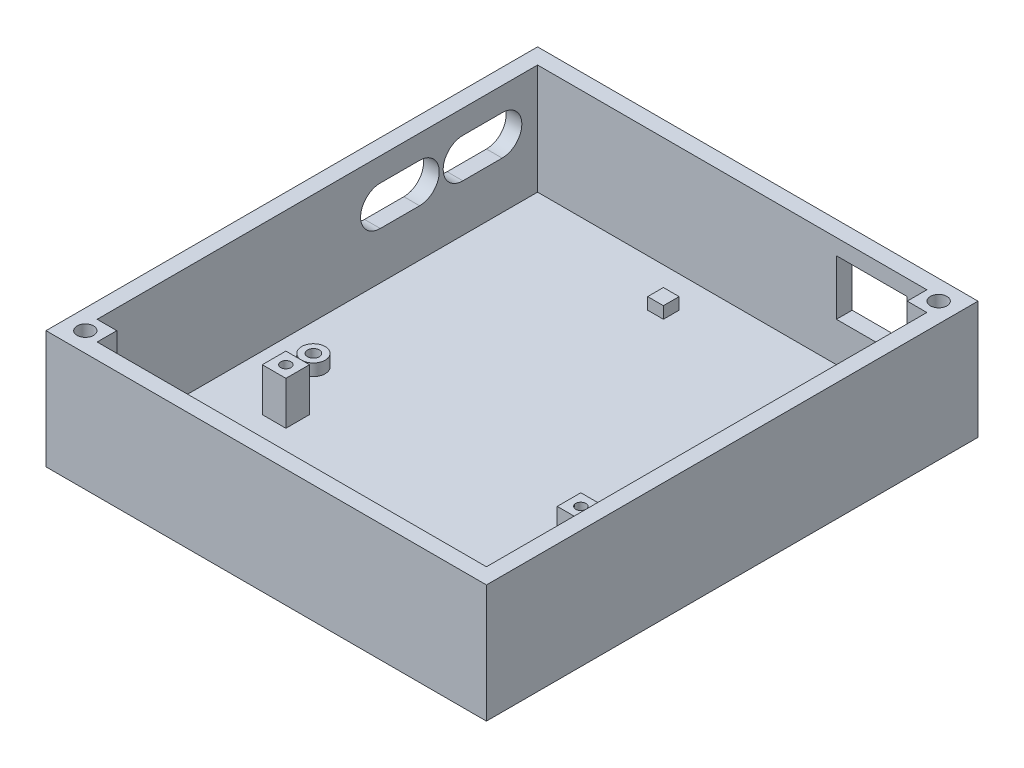
SolidWorks part; units mm, degrees
ref_plane "Front Plane" through (0, 0, 0) normal (0, 0, 1) x (1, 0, 0)
ref_plane "Top Plane" through (0, 0, 0) normal (0, 1, 0) x (1, 0, 0)
ref_plane "Right Plane" through (0, 0, 0) normal (1, 0, 0) x (0, 0, -1)
sketch "Sketch1" plane through (0, 0, 0) normal (0, 1, 0) x (1, 0, 0)
  line L1 (-56, -62.5) -> (56, -62.5)
  line L2 (-56, -62.5) -> (-56, 62.5)
  line L3 (-56, 62.5) -> (56, 62.5)
  line L4 (56, -62.5) -> (56, 62.5)
  line L5 (-56, -62.5) -> (56, 62.5) construction
  line L6 (-56, 62.5) -> (56, -62.5) construction
  point P0 (0, 0)
  dimension "D1" = 112
  dimension "D2" = 125
extrude "Boss-Extrude1" add sketch "Sketch1" along normal blind 2
sketch "Sketch2" plane through (0, 2, 0) normal (0, 1, 0) x (1, 0, 0)
  line L0 (-56, -62.5) -> (56, -62.5) construction
  line L1 (-12, 50.5) -> (-8, 50.5) construction
  line L2 (-12, 50.5) -> (-12, 46.5) construction
  line L3 (-12, 46.5) -> (-8, 46.5) construction
  line L4 (52, 53.5) -> (47, 53.5)
  line L5 (-8, 50.5) -> (-8, 46.5) construction
  line L6 (-56, 62.5) -> (-56, -62.5) construction
  line L7 (47, 53.5) -> (47, 58.5)
  line L8 (52, -58.5) -> (52, 58.5)
  line L9 (52, 58.5) -> (-52, 58.5)
  line L10 (-52, 58.5) -> (-52, -58.5)
  line L11 (-52, -58.5) -> (52, -58.5)
  line L12 (52, -58.5) -> (52, 53.5)
  line L13 (47, 58.5) -> (-52, 58.5)
  line L14 (-52, 58.5) -> (-52, -53.5)
  line L15 (-47, -58.5) -> (52, -58.5)
  line L16 (56, 62.5) -> (-56, 62.5) construction
  line L29 (-47, -58.5) -> (-47, -53.5)
  line L30 (-47, -53.5) -> (-52, -53.5)
  line L31 (56, -62.5) -> (56, 62.5) construction
  circle A0 centre (-42, -8.5) radius 1.5 construction
  circle A1 centre (38, -8.5) radius 1.5 construction
  circle A2 centre (-51, -57.5) radius 2.1
  circle A3 centre (51, 57.5) radius 2.1
  point P8 (0, 0)
  point P16 (54.7195, 58.7926)
  point P21 (-54.2044, -58.5)
  line M12 (56, -62.5) -> (56, 62.5)
  line M13 (56, 62.5) -> (-56, 62.5)
  line M14 (-56, 62.5) -> (-56, -62.5)
  line M15 (-56, -62.5) -> (56, -62.5)
  dimension "D1" = 3
  dimension "D13" = 4.2
  dimension "D15" = 4.2
  dimension "D18" = 5
  dimension "D2" = 80
  dimension "D3" = 5
  dimension "D5" = 8
  dimension "D6" = 62
  dimension "D7" = 5
  dimension "D8" = 14
  dimension "D9" = 4
  dimension "D10" = 4
  dimension "D11" = 40
  dimension "D12" = 5
  dimension "D14" = 5
  dimension "D16" = 5
  dimension "D17" = 5
  dimension "D4" = 4
extrude "Boss-Extrude2" add sketch "Sketch2" along normal blind 10 contours A0 | A1 | A3 A2 L29 L30 L14 L13 L7 L4 L12 L15 M15 M12 M13 M14 region at (48.9478, 2, -55.4478) region at (-48.9478, 2, 55.4478) region at (0, 2, 60.8216)
sketch "Sketch3" plane through (0, 2, 0) normal (0, 1, 0) x (1, 0, 0)
  line L0 (-32, -50.5) -> (-32, -25.5) construction
  line L1 (-35, -53.5) -> (40, -53.5) construction
  line L2 (-35, -53.5) -> (-35, -22.5) construction
  line L3 (-35, -22.5) -> (40, -22.5) construction
  line L4 (40, -53.5) -> (40, -22.5) construction
  line L5 (-32, -25.5) -> (37, -25.5) construction
  line L6 (37, -50.5) -> (37, -25.5) construction
  line L7 (-32, -50.5) -> (37, -50.5) construction
  line L8 (-38, -19.5) -> (43, -19.5)
  line L9 (43, -56.5) -> (43, -19.5)
  line L10 (-38, -56.5) -> (43, -56.5)
  line L11 (-38, -56.5) -> (-38, -19.5)
  line L12 (-47, -58.5) -> (52, -58.5) construction
  line L13 (-47, -58.5) -> (52, -58.5) construction
  line L14 (-32, -25.5) -> (-38, -25.5)
  line L15 (-32, -50.5) -> (-38, -50.5)
  line L16 (37, -25.5) -> (43, -25.5)
  line L17 (37, -50.5) -> (43, -50.5)
  line L18 (37, -25.5) -> (37, -19.5)
  line L19 (37, -50.5) -> (37, -56.5)
  line L20 (-32, -50.5) -> (-32, -56.5)
  line L21 (-32, -19.5) -> (-32, -25.5)
  circle A0 centre (-35, -22.5) radius 1.3
  circle A1 centre (40, -22.5) radius 1.3
  circle A2 centre (40, -53.5) radius 1.3
  circle A3 centre (-35, -53.5) radius 1.3
  point P17 (2.5, -22.5)
  point P19 (2.5, -58.5)
  dimension "D3" = 2.6
  dimension "D4" = 75
  dimension "D5" = 31
  dimension "D6" = 5
  dimension "D1" = 3
  dimension "D2" = 3
extrude "Boss-Extrude3" add sketch "Sketch3" along normal blind 11 contours L20 L15 L11 L10 A3 | L21 L8 L11 L14 A0 | L18 L16 L9 L8 A1 | L17 L19 L10 L9 A2 region at (-35, 2, 19.5849) region at (40, 2, 19.5849) region at (-35, 2, 50.5849) region at (42.9151, 2, 53.5)
sketch "Sketch5" plane through (0, 2, 0) normal (0, 1, 0) x (1, 0, 0)
  line L0 (-8, 50.5) -> (-8, 46.5) construction
  line L1 (-12, 50.5) -> (-8, 50.5) construction
  line L2 (-12, 50.5) -> (-12, 46.5) construction
  line L3 (-12, 46.5) -> (-8, 46.5) construction
  line L4 (-8, 50.5) -> (-8, 46.5)
  line L5 (-12, 50.5) -> (-8, 50.5)
  line L6 (-12, 50.5) -> (-12, 46.5)
  line L7 (-12, 46.5) -> (-8, 46.5)
  circle A0 centre (-42, -8.5) radius 3
  circle A1 centre (38, -8.5) radius 3
  circle A2 centre (38, -8.5) radius 1.5 construction
  circle A3 centre (38, -8.5) radius 1.5
  circle A4 centre (-42, -8.5) radius 1.5 construction
  circle A5 centre (-42, -8.5) radius 1.5
  dimension "D1" = 6
extrude "Boss-Extrude4" add sketch "Sketch5" along normal blind 3
sketch "Sketch6" plane through (0, 13, 0) normal (0, 1, 0) x (1, 0, 0)
  line L4 (-32, -56.5) -> (-32, -50.5)
  line L5 (-32, -50.5) -> (-38, -50.5)
  line L6 (-38, -50.5) -> (-38, -56.5)
  line L7 (-38, -56.5) -> (-32, -56.5)
  line L8 (-32, -56.5) -> (-32, -50.5)
  line L9 (-32, -50.5) -> (-38, -50.5)
  line L10 (-38, -50.5) -> (-38, -56.5)
  line L11 (-38, -56.5) -> (-32, -56.5)
  line L12 (37, -19.5) -> (37, -25.5)
  line L13 (37, -25.5) -> (43, -25.5)
  line L14 (43, -25.5) -> (43, -19.5)
  line L15 (43, -19.5) -> (37, -19.5)
  line L16 (37, -19.5) -> (37, -25.5)
  line L17 (37, -25.5) -> (43, -25.5)
  line L18 (43, -25.5) -> (43, -19.5)
  line L19 (43, -19.5) -> (37, -19.5)
  line L20 (43, -50.5) -> (37, -50.5)
  line L21 (37, -50.5) -> (37, -56.5)
  line L22 (37, -56.5) -> (43, -56.5)
  line L23 (43, -56.5) -> (43, -50.5)
  line L24 (43, -50.5) -> (37, -50.5)
  line L25 (37, -50.5) -> (37, -56.5)
  line L26 (37, -56.5) -> (43, -56.5)
  line L27 (43, -56.5) -> (43, -50.5)
  circle A0 centre (40, -53.5) radius 1.3 construction
  circle A1 centre (40, -22.5) radius 1.3
  circle A2 centre (40, -22.5) radius 1.3
  circle A3 centre (-35, -53.5) radius 1.3 construction
  circle A4 centre (40, -53.5) radius 1.3
  circle A5 centre (-35, -53.5) radius 1.3
  dimension "D1" = 0
  dimension "D2" = 0
  dimension "D3" = 0
  dimension "D4" = 0
extrude "Boss-Extrude5" add sketch "Sketch6" along normal blind 6.3
sketch "Sketch7" plane through (0, 12, 0) normal (0, 1, 0) x (1, 0, 0)
  line L4 (-56, -62.5) -> (56, -62.5)
  line L5 (56, -62.5) -> (56, 62.5)
  line L6 (56, 62.5) -> (-56, 62.5)
  line L7 (-56, 62.5) -> (-56, -62.5)
  line L8 (-56, -62.5) -> (56, -62.5)
  line L9 (56, -62.5) -> (56, 62.5)
  line L10 (56, 62.5) -> (-56, 62.5)
  line L11 (-56, 62.5) -> (-56, -62.5)
  circle M5 centre (51, 57.5) radius 2.1
  line M6 (47, 53.5) -> (52, 53.5)
  line M7 (52, 53.5) -> (52, -58.5)
  line M13 (52, 53.5) -> (52, -58.5)
  line M14 (52, -58.5) -> (-47, -58.5)
  line M15 (-47, -58.5) -> (-47, -53.5)
  line M16 (-47, -53.5) -> (-52, -53.5)
  line M17 (-52, -53.5) -> (-52, 58.5)
  line M18 (-52, 58.5) -> (47, 58.5)
  line M19 (47, 58.5) -> (47, 53.5)
  circle M22 centre (-51, -57.5) radius 2.1
  line M23 (-56, -62.5) -> (56, -62.5)
  line M24 (56, -62.5) -> (56, 62.5)
  line M25 (56, 62.5) -> (-56, 62.5)
  line M26 (-56, 62.5) -> (-56, -62.5)
  dimension "D1" = 0
extrude "Boss-Extrude6" add sketch "Sketch7" along normal blind 18 contours M26 M23 M24 M25 M22 M5 M7 M13 M14 M15 M16 M17 M18 M19 M6 region at (-54.3216, 12, 0)
sketch "Sketch9" plane through (-56, 0, 0) normal (-1, 0, 0) x (0, 0, 1)
  line L0 (-49.5, 19) -> (-39.5, 19) construction
  line L1 (-49.5, 24) -> (-39.5, 24)
  line L2 (-49.5, 14) -> (-39.5, 14)
  line L3 (-28.5, 19) -> (-18.5, 19) construction
  line L4 (-28.5, 24) -> (-18.5, 24)
  line L5 (-28.5, 14) -> (-18.5, 14)
  line L9 (-62.5, 30) -> (62.5, 30) construction
  line L10 (-62.5, 30) -> (-62.5, 0) construction
  arc A0 (-49.5, 24) -> (-49.5, 14) centre (-49.5, 19) ccw
  arc A1 (-39.5, 14) -> (-39.5, 24) centre (-39.5, 19) ccw
  arc A2 (-28.5, 24) -> (-28.5, 14) centre (-28.5, 19) ccw
  arc A3 (-18.5, 14) -> (-18.5, 24) centre (-18.5, 19) ccw
  point P2 (-44.5, 19)
  point P8 (-23.5, 19)
  point P23 (-34.5, 19)
  point P24 (-54.5, 19)
  dimension "D2" = 5
  dimension "D1" = 11
  dimension "D3" = 20
  dimension "D4" = 13
  dimension "D5" = 34
extrude "Cut-Extrude1" cut sketch "Sketch9" against normal up to next
sketch "Sketch10" plane through (0, 0, -62.5) normal (0, 0, -1) x (-1, 0, 0)
  line L3 (-24, 12) -> (-42, 12)
  line L5 (-56, 30) -> (-56, 0) construction
  line L6 (-42, 26) -> (-24, 26)
  line L7 (-42, 26) -> (-42, 12)
  line L8 (-24, 12) -> (-24, 26)
  line L9 (-56, 30) -> (56, 30) construction
  line L10 (-56, 0) -> (56, 0) construction
  point P8 (-33, 12)
  dimension "D1" = 14
  dimension "D2" = 23
  dimension "D3" = 18
  dimension "D4" = 4
  dimension "D5" = 12
extrude "Cut-Extrude2" cut sketch "Sketch10" against normal up to next
